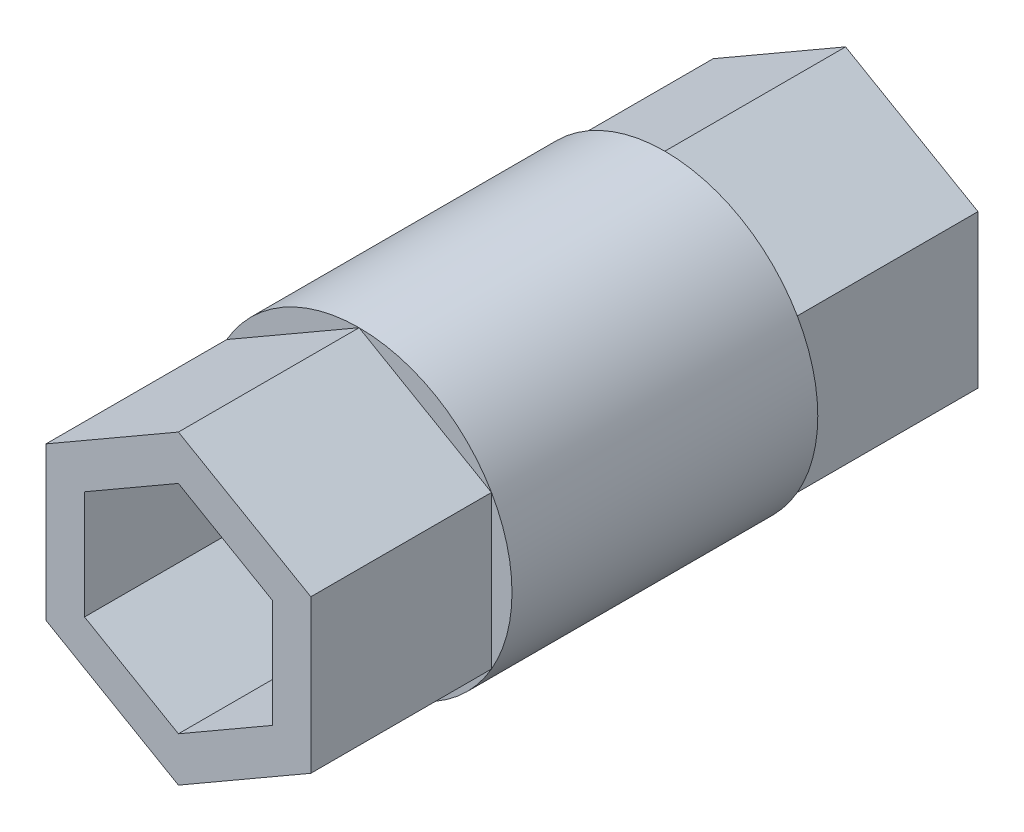
SolidWorks part; units mm, degrees
ref_plane "Front Plane" through (0, 0, 0) normal (0, 0, 1) x (1, 0, 0)
ref_plane "Top Plane" through (0, 0, 0) normal (0, 1, 0) x (1, 0, 0)
ref_plane "Right Plane" through (0, 0, 0) normal (1, 0, 0) x (0, 0, -1)
sketch "Sketch1" plane through (0, 0, 0) normal (0, 0, 1) x (1, 0, 0)
  line L1 (0, -11) -> (9.5263, -5.5)
  line L2 (9.5263, -5.5) -> (9.5263, 5.5)
  line L3 (9.5263, 5.5) -> (0, 11)
  line L4 (0, 11) -> (-9.5263, 5.5)
  line L5 (-9.5263, 5.5) -> (-9.5263, -5.5)
  line L6 (-9.5263, -5.5) -> (0, -11)
  circle A0 centre (0, 0) radius 11
  circle A1 centre (0, 0) radius 9.5263 construction
  circle A2 centre (0, 0) radius 6.4
  dimension "D1" = 22
  dimension "D2" = 12.8
extrude "Boss-Extrude1" add sketch "Sketch1" along normal mid plane 22 contours L4 A0 | L5 A0 | L5 L6 L1 L2 L3 L4 | L3 A0 | L2 A0 | L1 A0 | L6 A0 region at (-4.6176, -7.998, 0) region at (-5.0596, -8.7636, 0) region at (5.0596, -8.7636, 0) region at (10.1193, 0, 0) region at (-10.1193, 0, 0) region at (5.0596, 8.7636, 0) region at (-5.0596, 8.7636, 0)
extrude "Boss-Extrude2" add sketch "Sketch1<3>" along normal mid plane 48 contours L5 L6 L1 L2 L3 L4 A2 | A2 region at (-4.6176, -7.998, 0)
sketch "Sketch1<3>" plane through (0, 0, 0) normal (0, 0, 1) x (1, 0, 0) same geometry as "Sketch1"
sketch "Sketch2" plane through (0, 0, 24) normal (0, 0, 1) x (1, 0, 0)
  line L1 (0, -7.8) -> (6.755, -3.9)
  line L2 (6.755, -3.9) -> (6.755, 3.9)
  line L3 (6.755, 3.9) -> (0, 7.8)
  line L4 (0, 7.8) -> (-6.755, 3.9)
  line L5 (-6.755, 3.9) -> (-6.755, -3.9)
  line L6 (-6.755, -3.9) -> (0, -7.8)
  circle A0 centre (0, 0) radius 6.755 construction
  dimension "D1" = 15.6
extrude "Cut-Extrude3" cut sketch "Sketch2" against normal through all
